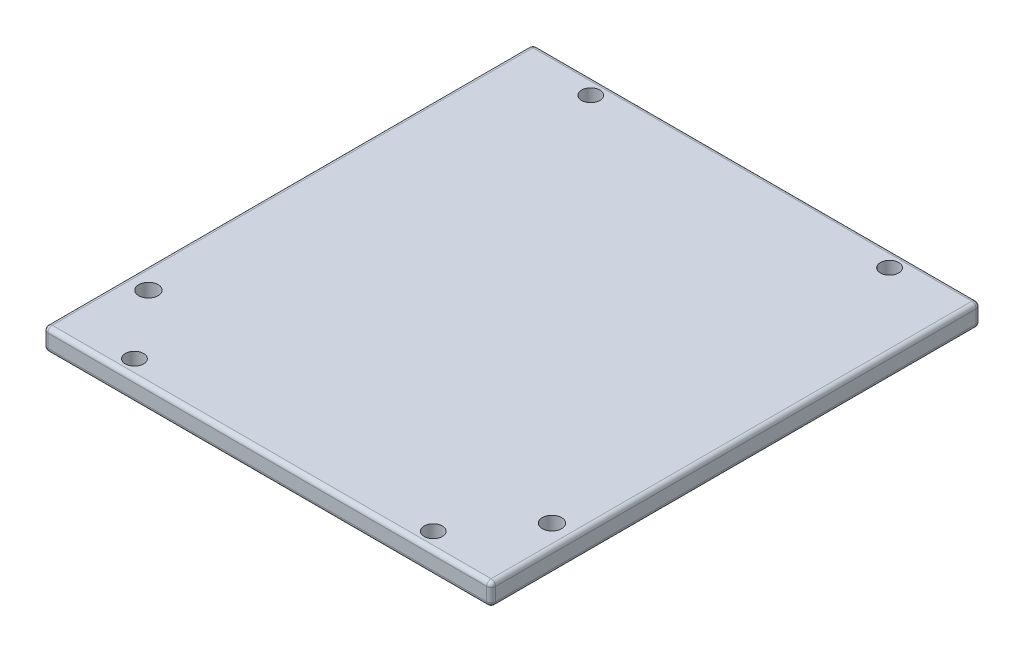
SolidWorks part; units mm, degrees
ref_plane "Front Plane" through (0, 0, 0) normal (0, 0, 1) x (1, 0, 0)
ref_plane "Top Plane" through (0, 0, 0) normal (0, 1, 0) x (1, 0, 0)
ref_plane "Right Plane" through (0, 0, 0) normal (1, 0, 0) x (0, 0, -1)
sketch "Sketch1" plane through (0, 0, 0) normal (0, 1, 0) x (1, 0, 0)
  line L0 (40.5, 88.55) -> (40.5, 0) construction
  line L1 (0, 0) -> (81, 0)
  line L2 (0, 0) -> (0, 88.55)
  line L3 (0, 88.55) -> (81, 88.55)
  line L4 (81, 0) -> (81, 88.55)
  circle A0 centre (4, 15) radius 1.75
  circle A1 centre (13.475, 3) radius 1.65
  circle A2 centre (13.475, 85.55) radius 1.65
  circle A3 centre (77, 15) radius 1.75
  circle A4 centre (67.525, 3) radius 1.65
  circle A5 centre (67.525, 85.55) radius 1.65
  point P12 (4, 15)
  dimension "D3" = 4
  dimension "D4" = 13.475
  dimension "D5" = 3
  dimension "D6" = 3
  dimension "D7" = 15
  dimension "D8" = 3.3
  dimension "D9" = 3.3
  dimension "D10" = 3.5
  dimension "D11" = 13.475
  dimension "D1" = 81
  dimension "D2" = 88.55
extrude "Boss-Extrude1" add sketch "Sketch1" along normal blind 4
fillet "Fillet3" radius 0.8 12 edges at (0, 2, -88.55) (0, 4, -44.275) (0, 0, -44.275) (0, 2, 0) (40.5, 4, 0) (40.5, 0, 0) (81, 2, 0) (81, 4, -44.275) (81, 0, -44.275) (81, 2, -88.55) (40.5, 4, -88.55) (40.5, 0, -88.55)
sketch "Sketch2" plane through (0, 0, 0) normal (0, -1, 0) x (1, 0, 0)
  line L1 (10.75, -24) -> (15.75, -24)
  line L2 (10.75, -24) -> (10.75, -44)
  line L3 (10.75, -44) -> (15.75, -44)
  line L4 (15.75, -24) -> (15.75, -44)
  circle A1 centre (4, -15) radius 1.75 construction
  dimension "D3" = 9
  dimension "D1" = 6.75
  dimension "D2" = 20
  dimension "D4" = 5
extrude "Boss-Extrude2" add sketch "Sketch2" along normal blind 8.8
sketch "Sketch5" plane through (0, 0, -44) normal (0, 0, -1) x (-1, 0, 0)
  line L0 (-15.75, -8.8) -> (-15.75, 0) construction
  line L1 (-10.75, 0) -> (-13.95, 0)
  line L2 (-10.75, 0) -> (-10.75, -6.8)
  line L3 (-10.75, -6.8) -> (-13.95, -6.8)
  line L4 (-13.95, 0) -> (-13.95, -6.8)
  dimension "D1" = 6.8
  dimension "D2" = 1.8
extrude "Cut-Extrude1" cut sketch "Sketch5" against normal through all
fillet "Fillet1" radius 3 1 edges at (15.75, 0, -34) second distance 5 first distance on face at (13.475, 0, -1.35)
fillet "Fillet2" radius 0.5 9 edges at (13.25, -8.8, -24) (13.25, -8.8, -44) (10.75, -7.8, -24) (10.75, -7.8, -44) (10.75, -6.8, -34) (13.95, -3.4, -44) (13.95, -3.4, -24) (10.75, -8.8, -34) (15.75, -8.8, -34)
ref_axis "Axis1" through (40.5, 0, -0.8) along (0, 0, -1)
ref_plane "Plane1" through (40.5, 0, 0) normal (-1, 0, 0) x (0, 0, -1)
mirror "Mirror1" about plane through (40.5, 0, 0) normal (-1, 0, 0) of "Fillet2", "Fillet1", "Cut-Extrude1", "Boss-Extrude2"
